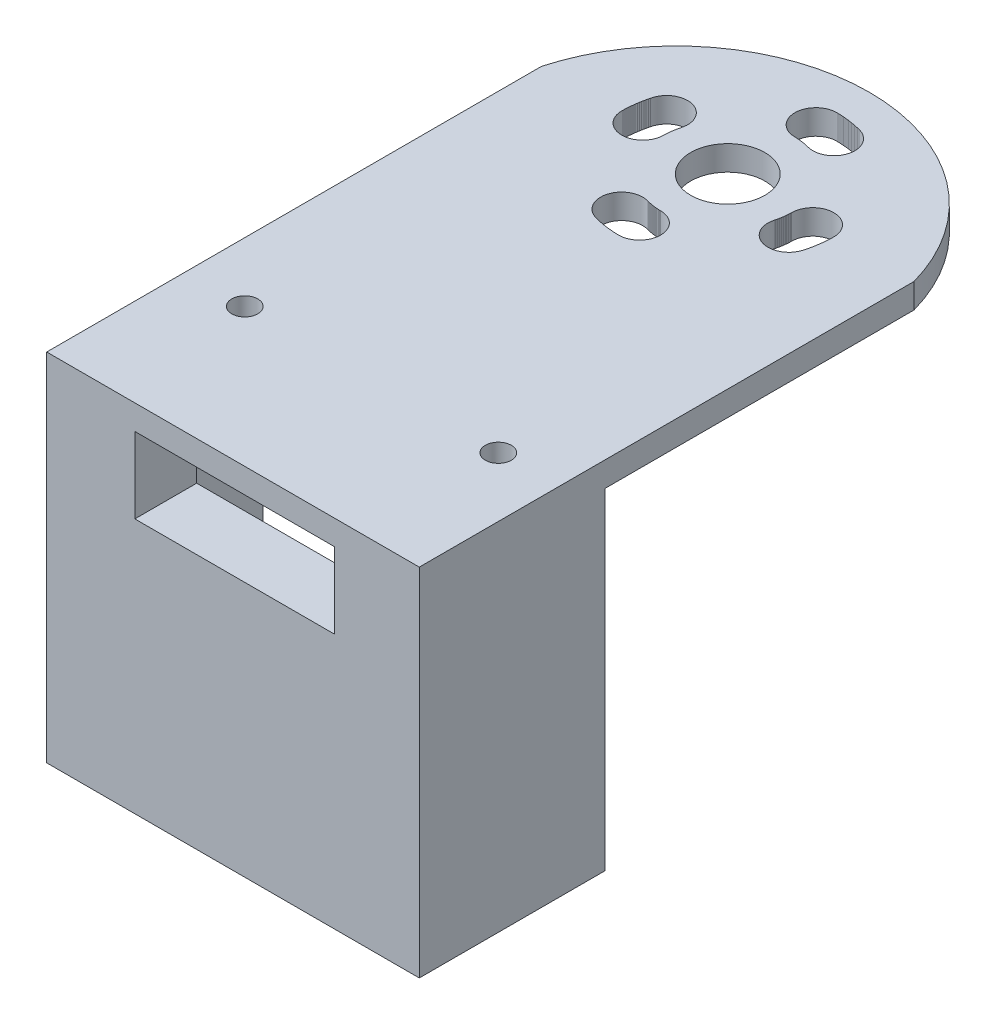
SolidWorks part; units mm, degrees
ref_plane "Front Plane" through (0, 0, 0) normal (0, 0, 1) x (1, 0, 0)
ref_plane "Top Plane" through (0, 0, 0) normal (0, 1, 0) x (1, 0, 0)
ref_plane "Right Plane" through (0, 0, 0) normal (1, 0, 0) x (0, 0, -1)
sketch "Sketch2" plane through (0, 0, 0) normal (0, 1, 0) x (1, 0, 0)
  line L0 (15.061, 0) -> (15.061, 32)
  line L1 (-12.561, 2.5) -> (12.561, 2.5)
  line L2 (-12.561, 2.5) -> (-12.561, 32)
  line L4 (12.561, 2.5) -> (12.561, 32)
  line L5 (15.061, 32) -> (12.561, 32)
  line L7 (-15.061, 32) -> (-15.061, 0)
  line L8 (-15.061, 0) -> (15.061, 0)
  line L10 (-15.061, 32) -> (-12.561, 32)
  point P4 (0, 2.5)
  point P12 (0, 0)
  dimension "D1" = 2.5
  dimension "D2" = 2.5
  dimension "D3" = 29.5
  dimension "D4" = 25.122
extrude "Boss-Extrude1" add sketch "Sketch2" along normal blind 32.5
sketch "Sketch4" plane through (0, 0, 0) normal (0, -1, 0) x (1, 0, 0)
  line L10 (-7.561, -6) -> (-7.561, 0)
  line L13 (-12.561, -2.5) -> (-12.561, -32) construction
  line L18 (-12.561, -10) -> (-7.561, -6)
  line L23 (12.561, -32) -> (12.561, -2.5) construction
  line L26 (12.561, -10) -> (7.561, -6)
  line L33 (-15.061, -32) -> (-15.061, 0) construction
  line L36 (15.061, 0) -> (15.061, -32) construction
  line L38 (-7.561, 0) -> (-15.061, 0)
  line L39 (7.561, -6) -> (7.561, 0)
  line L40 (7.561, 0) -> (15.061, 0)
  line L41 (-15.061, 0) -> (-15.061, -32)
  line L42 (-15.061, -32) -> (-12.561, -32)
  line L43 (-12.561, -32) -> (-15.061, -32) construction
  line L44 (-12.561, -32) -> (-12.561, -10)
  line L45 (12.561, -10) -> (12.561, -32)
  line L46 (12.561, -32) -> (15.061, -32)
  line L47 (15.061, -32) -> (15.061, 0)
  circle A2 centre (-10.2499, -4.95) radius 1.05
  circle A5 centre (10.2499, -4.95) radius 1.05
  dimension "D4" = 6
  dimension "D5" = 2.1
  dimension "D1" = 7.5
  dimension "D2" = 7.5
  dimension "D3" = 10
extrude "Boss-Extrude2" add sketch "Sketch4" along normal blind 2.5
sketch "Sketch5" plane through (0, 32.5, 0) normal (0, 1, 0) x (1, 0, 0)
  line L0 (-15.061, 32) -> (-10.2499, 32)
  line L9 (-10.2499, 32) -> (-6.25, 26)
  line L13 (-15.061, 0) -> (15.061, 0) construction
  line L14 (15.061, 0) -> (-15.061, 0)
  line L15 (-15.061, 0) -> (-15.061, 32)
  line L20 (15.061, 0) -> (15.061, 32)
  line L21 (-6.25, 26) -> (6.25, 26)
  line L22 (6.25, 26) -> (10.2499, 32)
  line L23 (10.2499, 32) -> (15.061, 32)
  circle A0 centre (-10.2499, 4.95) radius 1.05 construction
  circle A1 centre (-10.2499, 8.7) radius 1.05
  circle A2 centre (10.2499, 8.7) radius 1.05
  point P6 (0, 26)
  dimension "D4" = 0
  dimension "D1" = 8.7
  dimension "D2" = 12.5
  dimension "D3" = 20.4998
  dimension "D5" = 6
extrude "Boss-Extrude3" add sketch "Sketch5" along normal blind 3
sketch "Sketch6" plane through (-15.061, 0, 0) normal (-1, 0, 0) x (0, 0, 1)
  line L1 (-32, -2.5) -> (-32, 29.6998)
  line L5 (-32, 35.5) -> (-32, -2.5) construction
  line L7 (0, 35.5) -> (0, -2.5) construction
  line L8 (-12.5, -2.5) -> (-12.5, 35.5)
  line L9 (-32, 35.5) -> (0, 35.5) construction
  line L10 (-12.5, 35.5) -> (-32, 35.5)
  line L11 (-32, 35.5) -> (-32, 29.6998)
  line L12 (0, -2.5) -> (-32, -2.5) construction
  line L13 (-32, -2.5) -> (-12.5, -2.5)
  dimension "D2" = 12.5
extrude "Cut-Extrude1" cut sketch "Sketch6" against normal through all
ref_plane "Plane1" through (0, 16.5, 0) normal (0, -1, 0) x (-1, 0, 0)
sketch "Sketch13" plane through (0, 0, 0) normal (0, 0, 1) x (1, 0, 0)
  line L1 (-15.061, 35.5) -> (15.061, 35.5)
  line L2 (-15.061, 35.5) -> (-15.061, -2.5)
  line L3 (-15.061, -2.5) -> (15.061, -2.5)
  line L4 (15.061, 35.5) -> (15.061, -2.5)
extrude "Boss-Extrude7" add sketch "Sketch13" along normal blind 2.5
sketch "Sketch14" plane through (0, 0, 2.5) normal (0, 0, 1) x (1, 0, 0)
  line L0 (15.061, 35.5) -> (-15.061, 35.5) construction
  line L1 (-7.9361, 35.5) -> (8.206, 35.5)
  line L2 (-7.9361, 35.5) -> (-7.9361, 29.3758)
  line L3 (-7.9361, 29.3758) -> (8.206, 29.3758)
  line L4 (8.206, 35.5) -> (8.206, 29.3758)
extrude "Cut-Extrude2" cut sketch "Sketch14" against normal through all both and the other way through all
sketch "Sketch15" plane through (0, 0, -12.5) normal (0, 0, -1) x (-1, 0, 0)
  line L0 (15.061, -2.5) -> (15.061, 35.5) construction
  line L1 (-15.061, 35.5) -> (15.061, 35.5)
  line L2 (-15.061, 35.5) -> (-15.061, 37.5)
  line L3 (-15.061, 37.5) -> (15.061, 37.5)
  line L4 (15.061, 35.5) -> (15.061, 37.5)
  dimension "D1" = 2
extrude "Boss-Extrude8" add sketch "Sketch15" against normal up to surface (15 mm away) and the other way blind 40 up to face at (0.0675, 24.469, 2.5)
sketch "Sketch16" plane through (0, 37.5, 0) normal (0, 1, 0) x (1, 0, 0)
  line L0 (-15.061, -2.5) -> (15.061, -2.5) construction
  circle A0 centre (0, 37.5) radius 3
  dimension "D1" = 6
  dimension "D2" = 40
extrude "Cut-Extrude3" cut sketch "Sketch16" against normal through all both and the other way through all
sketch "Sketch17" plane through (0, 37.5, 0) normal (0, 1, 0) x (1, 0, 0)
  circle A0 centre (1.8162, 44.2603) radius 1.7
  circle A2 centre (0, 37.5) radius 3 construction
  dimension "D1" = 3.4
  dimension "D2" = 1.8162
  dimension "D3" = 6.7603
extrude "Cut-Extrude4" cut sketch "Sketch17" against normal through all both and the other way through all
ref_axis "Axis1" through (0, 35.5, -37.5) along (0, 1, 0)
pattern_circular "CirPattern1" count 15 every 1 about axis through (0, 35.5, -37.5) along (0, 1, 0) of "Cut-Extrude4"
pattern_circular "CirPattern2" count 4 over 360 about axis through (0, 35.5, -37.5) along (0, 1, 0) of "CirPattern1"
sketch "Sketch19" plane through (0, 0, -12.5) normal (0, 0, -1) x (-1, 0, 0)
  line L1 (-15.061, 8.7299) -> (15.061, 8.7299)
  line L2 (-15.061, 8.7299) -> (-15.061, -7.1783)
  line L3 (-15.061, -7.1783) -> (15.061, -7.1783)
  line L4 (15.061, 8.7299) -> (15.061, -7.1783)
extrude "Cut-Extrude5" cut sketch "Sketch19" against normal through all both and the other way through all
sketch "Sketch23" plane through (0, 37.5, 0) normal (0, 1, 0) x (1, 0, 0)
  line L9 (-15.061, 52.5) -> (-15.061, -2.5) construction
  line L10 (15.061, 52.5) -> (15.061, -2.5) construction
  line L11 (-15.061, 37.5) -> (-15.061, 55.7627)
  line L12 (-15.061, 55.7627) -> (15.061, 55.1353)
  line L13 (15.061, 55.1353) -> (15.061, 37.5)
  arc A1 (-15.061, 37.5) -> (15.061, 37.5) centre (0, 33.3084) cw
extrude "Cut-Extrude8" cut sketch "Sketch23" against normal through all both and the other way through all
sketch "Sketch24" plane through (0, 32.5, 0) normal (0, -1, 0) x (1, 0, 0)
  circle A0 centre (-10.2499, -8.7) radius 1.05
  circle A1 centre (10.2499, -8.7) radius 1.05
extrude "Cut-Extrude9" cut sketch "Sketch24" against normal through all
